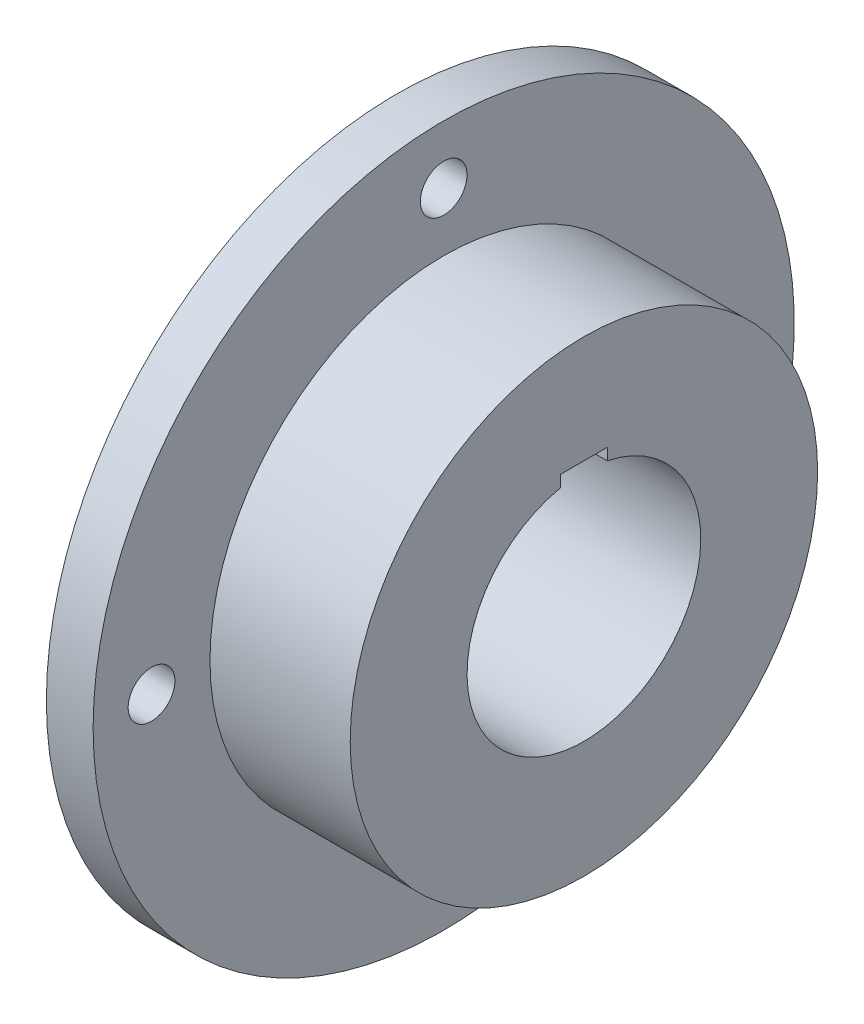
SolidWorks part; units mm, degrees
ref_plane "Front Plane" through (0, 0, 0) normal (0, 0, 1) x (1, 0, 0)
ref_plane "Top Plane" through (0, 0, 0) normal (0, 1, 0) x (1, 0, 0)
ref_plane "Right Plane" through (0, 0, 0) normal (1, 0, 0) x (0, 0, -1)
sketch "Sketch1" plane through (0, 0, 0) normal (1, 0, 0) x (0, 0, -1)
  circle A0 centre (0, 0) radius 10
  circle A1 centre (0, 0) radius 20
  dimension "D1" = 20
  dimension "D2" = 40
extrude "Boss-Extrude1" add sketch "Sketch1" along normal mid plane 14
sketch "Sketch2" plane through (-7, 0, 0) normal (-1, 0, 0) x (0, 0, 1)
  circle A0 centre (0, 0) radius 30
  circle A1 centre (0, 0) radius 10 construction
  circle A2 centre (0, 0) radius 10
  dimension "D1" = 60
extrude "Boss-Extrude2" add sketch "Sketch2" along normal mid plane 4
sketch "Sketch3" plane through (-5, 0, 0) normal (1, 0, 0) x (0, 0, -1)
  line L0 (0, 0) -> (0, 25) construction
  circle A0 centre (0, 25) radius 2
  circle A1 centre (0, 0) radius 25 construction
  circle A2 centre (25, 0) radius 2
  circle A3 centre (0, -25) radius 2
  circle A4 centre (-25, 0) radius 2
  point P14 (0, 0)
  dimension "D1" = 4
  dimension "D2" = 50
  dimension "D4" = 25
  dimension "D5" = 25
  dimension "D3" = 4
extrude "Cut-Extrude1" cut sketch "Sketch3" against normal through all
sketch "Sketch4" plane through (7, 0, 0) normal (1, 0, 0) x (0, 0, -1)
  line L0 (0, 0) -> (0, 17.0623) construction
  line L1 (2, 10.798) -> (-2, 10.798)
  line L2 (-2, 10.798) -> (-2, 9.798)
  line L3 (2, 10.798) -> (2, 9.798)
  circle A0 centre (0, 0) radius 10 construction
  circle A1 centre (0, 0) radius 10
  point P10 (0, 10.798)
  circle M5 centre (0, 0) radius 10
  dimension "D1" = 1
  dimension "D2" = 2
extrude "Cut-Extrude2" cut sketch "Sketch4" against normal through all contours L0 L1 L2 M5 | L0 A1 L3 L1 region at (7, 10.3634, 1.0388) region at (7, 10.3634, -1.0388)
equation "\"shaft-diameter\" =20mm"
equation "\"D1@Sketch1\"=\"shaft-diameter\""
